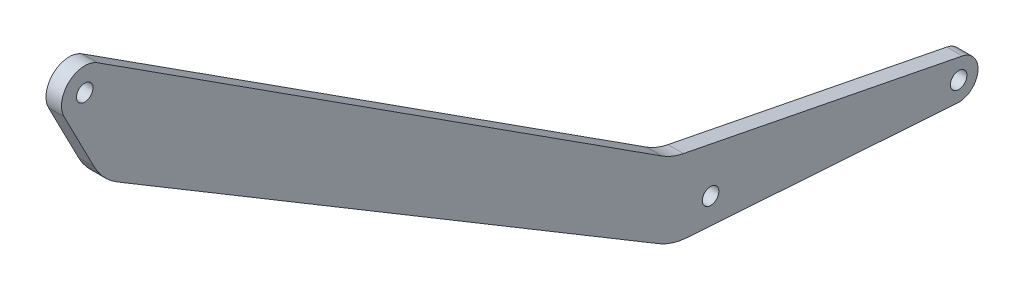
SolidWorks part; units mm, degrees
ref_plane "Front Plane" through (0, 0, 0) normal (0, 0, 1) x (1, 0, 0)
ref_plane "Top Plane" through (0, 0, 0) normal (0, 1, 0) x (1, 0, 0)
ref_plane "Right Plane" through (0, 0, 0) normal (1, 0, 0) x (0, 0, -1)
ref_plane "Plane1" through (-76.9133, 0, 0) normal (1, 0, 0) x (0, 0, -1)
sketch "Sketch1" plane through (-76.9133, 0, 0) normal (1, 0, 0) x (0, 0, -1)
  line L0 (535.7661, 896.8306) -> (535.7661, 915.8806) construction
  line L1 (434.1661, 906.5188) -> (434.1661, 925.5688) construction
  line L2 (177.8, 1090.4307) -> (434.1661, 925.5688) construction
  line L3 (139.7, 1090.4307) -> (177.8, 1090.4307) construction
  line L4 (535.7661, 896.8306) -> (535.7661, 915.8806) construction
  line L5 (434.1661, 906.5188) -> (434.1661, 925.5688) construction
  line L6 (177.8, 1090.4307) -> (434.1661, 925.5688) construction
  line L7 (139.7, 1090.4307) -> (177.8, 1090.4307) construction
  line L8 (535.2188, 907.962) -> (418.2911, 916.0438)
  line L9 (537.2996, 923.6685) -> (418.2911, 947.1021)
  line L10 (169.3326, 1086.0686) -> (184.9514, 1055.7506)
  line L11 (184.9514, 1055.7506) -> (418.2911, 916.0438)
  line L12 (418.2911, 947.1021) -> (182.9519, 1098.4422)
  circle A0 centre (177.8, 1090.4307) radius 3.3782
  circle A1 centre (434.1661, 925.5688) radius 3.3782
  circle A2 centre (535.7661, 915.8806) radius 3.3782
  arc A3 (535.2188, 907.962) -> (537.2996, 923.6685) centre (535.7661, 915.8806) ccw
  arc A5 (182.9519, 1098.4422) -> (169.3326, 1086.0686) centre (177.8, 1090.4307) ccw
  arc A6 (537.2996, 923.6685) -> (535.2188, 907.962) centre (535.7661, 915.8806) ccw construction
  arc A7 (169.3326, 1086.0686) -> (185.8114, 1085.2788) centre (177.8, 1090.4307) ccw construction
  arc A8 (185.8114, 1085.2788) -> (182.9519, 1098.4422) centre (177.8, 1090.4307) ccw construction
  spline S0 degree 3 poles (935.6767, 939.7163) (940.3147, 942.1548) (935.2529, 940.0507) (930.9716, 938.764) (920.6916, 935.461) (907.9553, 931.9087) (891.2949, 927.4743) (871.5218, 922.6042) (848.5739, 917.4165) (822.7695, 912.1503) (794.3904, 907.0475) (763.8436, 902.4482) (731.6326, 898.5836) (698.2942, 895.5048) (664.3294, 893.3038) (630.2914, 892.1587) (596.9177, 892.4579) (565.0805, 894.155) (535.5455, 896.7257) (508.8897, 899.7641) (485.4664, 902.8148) (465.3261, 905.1664) (448.3721, 906.4646) (434.4368, 906.7165) (423.4463, 905.9074) (416.5733, 904.5379) (412.9407, 903.1204) (411.5732, 902.4729) (410.4746, 901.8174) (409.7947, 901.3358) (409.3397, 900.9203) (409.0422, 900.6195) (408.7846, 900.3039) (408.5873, 899.9553) (408.4178, 899.5844) (408.2374, 899.0451) (408.051, 898.3239) (407.9116, 897.2265) (407.8599, 894.9991) (408.6865, 890.8402) (411.376, 884.946) (416.2539, 878.2548) (423.1327, 871.4111) (431.9816, 864.5947) (442.7539, 857.9825) (455.382, 851.7275) (469.765, 845.9615) (485.7865, 840.8065) (503.3041, 836.37) (522.1586, 832.7575) (542.1676, 830.0521) (563.1459, 828.3505) (584.9266, 827.7965) (607.3492, 828.4639) (630.2782, 830.4035) (653.5854, 833.657) (677.1845, 838.2437) (700.9897, 844.1113) (724.9284, 850.9153) (748.8232, 858.3979) (772.4019, 866.3681) (795.3921, 874.6046) (817.5075, 882.9123) (838.4515, 891.1278) (857.9391, 899.0809) (875.6775, 906.6433) (891.4161, 913.7156) (904.9213, 920.2497) (916.21, 926.5709) (924.8872, 932.3286) (932.3848, 937.3638) (935.6767, 939.7163) (940.3147, 942.1548) (935.2529, 940.0507) knots -0.014576 -0.006911 -0.001813 0 0.001841 0.007308 0.016237 0.028456 0.043801 0.062126 0.08324 0.106896 0.132817 0.160613 0.189791 0.219873 0.250457 0.281127 0.311257 0.339999 0.366671 0.390812 0.411995 0.430069 0.445224 0.457619 0.467425 0.474786 0.47628 0.477884 0.47884 0.479711 0.480113 0.480492 0.480846 0.481203 0.481564 0.48194 0.482727 0.483559 0.484903 0.488692 0.494806 0.502149 0.510796 0.520764 0.532062 0.544666 0.558541 0.573612 0.589803 0.60701 0.625107 0.643967 0.663469 0.683551 0.704142 0.725196 0.74668 0.768633 0.790977 0.813463 0.835827 0.857772 0.879003 0.899228 0.918151 0.935487 0.950987 0.964428 0.975828 0.985424 0.993089 0.998187 1 1.001841 1.007308 1.016237 only from (939.324, 941.6889) to (939.324, 941.6889) construction
  spline S1 degree 3 poles (935.6767, 939.7163) (940.3147, 942.1548) (935.2529, 940.0507) (930.9716, 938.764) (920.6916, 935.461) (907.9553, 931.9087) (891.2949, 927.4743) (871.5218, 922.6042) (848.5739, 917.4165) (822.7695, 912.1503) (794.3904, 907.0475) (763.8436, 902.4482) (731.6326, 898.5836) (698.2942, 895.5048) (664.3294, 893.3038) (630.2914, 892.1587) (596.9177, 892.4579) (565.0805, 894.155) (535.5455, 896.7257) (508.8897, 899.7641) (485.4664, 902.8148) (465.3261, 905.1664) (448.3721, 906.4646) (434.4368, 906.7165) (423.4463, 905.9074) (416.5733, 904.5379) (412.9407, 903.1204) (411.5732, 902.4729) (410.4746, 901.8174) (409.7947, 901.3358) (409.3397, 900.9203) (409.0422, 900.6195) (408.7846, 900.3039) (408.5873, 899.9553) (408.4178, 899.5844) (408.2374, 899.0451) (408.051, 898.3239) (407.9116, 897.2265) (407.8599, 894.9991) (408.6865, 890.8402) (411.376, 884.946) (416.2539, 878.2548) (423.1327, 871.4111) (431.9816, 864.5947) (442.7539, 857.9825) (455.382, 851.7275) (469.765, 845.9615) (485.7865, 840.8065) (503.3041, 836.37) (522.1586, 832.7575) (542.1676, 830.0521) (563.1459, 828.3505) (584.9266, 827.7965) (607.3492, 828.4639) (630.2782, 830.4035) (653.5854, 833.657) (677.1845, 838.2437) (700.9897, 844.1113) (724.9284, 850.9153) (748.8232, 858.3979) (772.4019, 866.3681) (795.3921, 874.6046) (817.5075, 882.9123) (838.4515, 891.1278) (857.9391, 899.0809) (875.6775, 906.6433) (891.4161, 913.7156) (904.9213, 920.2497) (916.21, 926.5709) (924.8872, 932.3286) (932.3848, 937.3638) (935.6767, 939.7163) (940.3147, 942.1548) (935.2529, 940.0507) knots -0.014576 -0.006911 -0.001813 0 0.001841 0.007308 0.016237 0.028456 0.043801 0.062126 0.08324 0.106896 0.132817 0.160613 0.189791 0.219873 0.250457 0.281127 0.311257 0.339999 0.366671 0.390812 0.411995 0.430069 0.445224 0.457619 0.467425 0.474786 0.47628 0.477884 0.47884 0.479711 0.480113 0.480492 0.480846 0.481203 0.481564 0.48194 0.482727 0.483559 0.484903 0.488692 0.494806 0.502149 0.510796 0.520764 0.532062 0.544666 0.558541 0.573612 0.589803 0.60701 0.625107 0.643967 0.663469 0.683551 0.704142 0.725196 0.74668 0.768633 0.790977 0.813463 0.835827 0.857772 0.879003 0.899228 0.918151 0.935487 0.950987 0.964428 0.975828 0.985424 0.993089 0.998187 1 1.001841 1.007308 1.016237 only from (939.324, 941.6889) to (939.324, 941.6889) construction
  dimension "D1" = 6.7564
  dimension "D2" = 6.7564
  dimension "D3" = 6.7564
  dimension "D4" = 15.875
  dimension "D5" = 30
  dimension "D6" = 19.05
  dimension "D7" = 148.166
  dimension "D8" = 15.875
  dimension "D9" = 9.525
extrude "Boss-Extrude1" add sketch "Sketch1" along normal mid plane 6.35
fillet "Fillet1" radius 25.4 3 edges at (-76.9133, 1055.7506, -184.9514) (-76.9133, 947.1021, -418.2911) (-76.9133, 916.0438, -418.2911)
